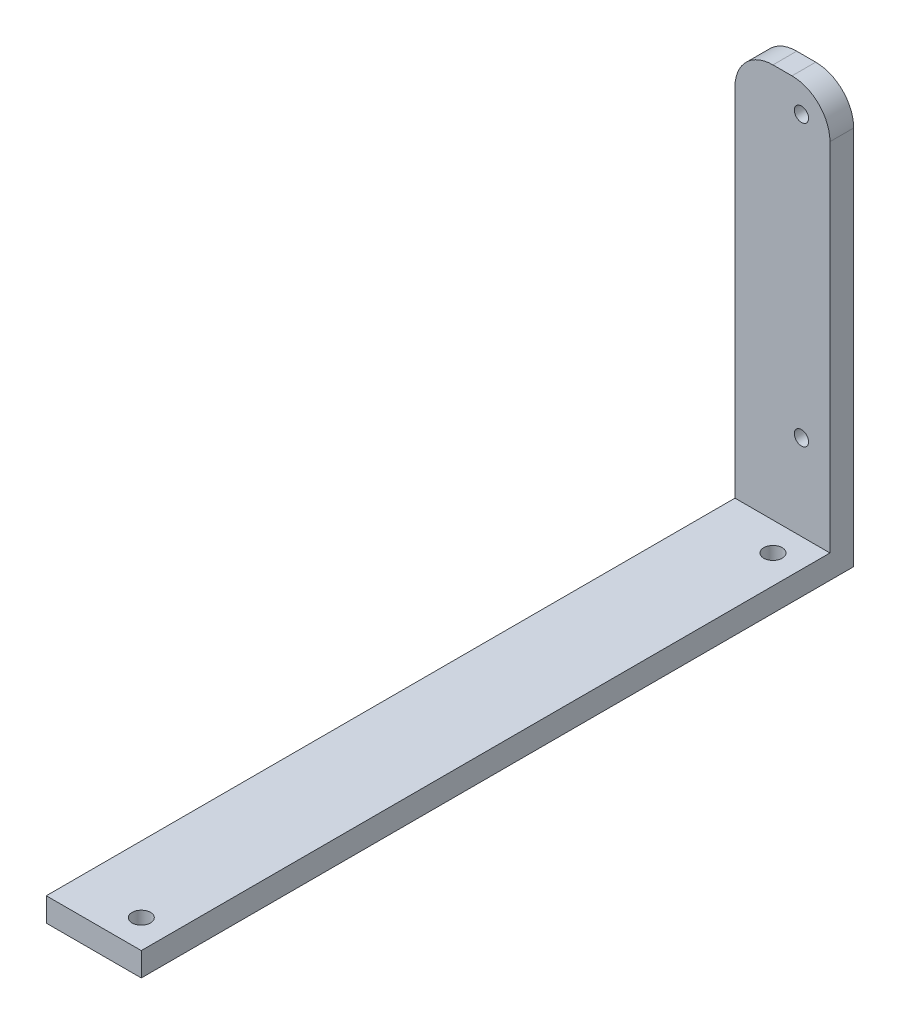
SolidWorks part; units mm, degrees
ref_plane "Front Plane" through (0, 0, 0) normal (0, 0, 1) x (1, 0, 0)
ref_plane "Top Plane" through (0, 0, 0) normal (0, 1, 0) x (1, 0, 0)
ref_plane "Right Plane" through (0, 0, 0) normal (1, 0, 0) x (0, 0, -1)
sketch "Sketch1" plane through (0, 0, 0) normal (0, 0, 1) x (1, 0, 0)
  line L1 (0, 0) -> (20, 0)
  line L2 (0, 0) -> (0, 88)
  line L3 (0, 88) -> (20, 88)
  line L4 (20, 0) -> (20, 88)
  circle A0 centre (14, 82) radius 1.5
  circle A1 centre (14, 23) radius 1.5
  dimension "D3" = 3
  dimension "D1" = 88
  dimension "D2" = 20
  dimension "D4" = 6
  dimension "D5" = 6
  dimension "D6" = 59
extrude "Boss-Extrude1" add sketch "Sketch1" along normal blind 5
sketch "Sketch2" plane through (0, 0, 5) normal (0, 0, 1) x (1, 0, 0)
  line L0 (20, 0) -> (20, 88) construction
  line L1 (0, 0) -> (20, 0)
  line L2 (0, 0) -> (0, 5)
  line L3 (0, 5) -> (20, 5)
  line L4 (20, 0) -> (20, 5)
  dimension "D1" = 5
extrude "Boss-Extrude2" add sketch "Sketch2" along normal blind 145
fillet "Fillet1" radius 8 2 edges at (20, 88, 2.5) (0, 88, 2.5)
sketch "Sketch3" plane through (0, 5, 0) normal (0, 1, 0) x (1, 0, 0)
  line L0 (20, -150) -> (0, -150) construction
  line L1 (20, -5) -> (0, -5) construction
  line L3 (20, -150) -> (20, -5) construction
  circle A0 centre (14, -144) radius 1.9394
  circle A1 centre (14, -11) radius 1.9394
  dimension "D4" = 6
  dimension "D3" = 3.8788
  dimension "D1" = 6
  dimension "D2" = 6
extrude "Cut-Extrude1" cut sketch "Sketch3" against normal through all
